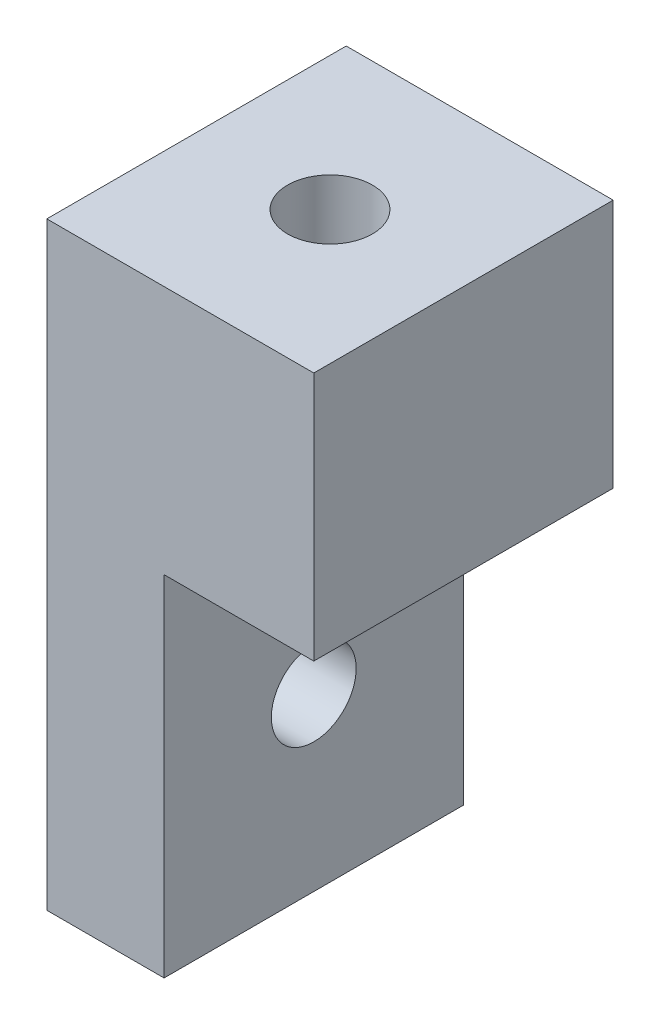
SolidWorks part; units mm, degrees
ref_plane "Front Plane" through (0, 0, 0) normal (0, 0, 1) x (1, 0, 0)
ref_plane "Top Plane" through (0, 0, 0) normal (0, 1, 0) x (1, 0, 0)
ref_plane "Right Plane" through (0, 0, 0) normal (1, 0, 0) x (0, 0, -1)
sketch "Sketch1" plane through (0, 0, 0) normal (0, 0, 1) x (1, 0, 0)
  line L0 (-0.325, -6) -> (-0.325, 1)
  line L1 (-2.675, 6) -> (2.675, 6)
  line L2 (-2.675, 6) -> (-2.675, -6)
  line L3 (-2.675, -6) -> (2.675, -6)
  line L4 (2.675, 6) -> (2.675, -6)
  line L5 (-2.675, 6) -> (2.675, -6) construction
  line L6 (-2.675, -6) -> (2.675, 6) construction
  line L7 (-0.325, 1) -> (2.675, 1)
  line L8 (2.675, 1) -> (2.675, -6)
  point P0 (0, 0)
  dimension "D1" = 0
  dimension "D2" = 12
  dimension "D3" = 3
  dimension "D4" = 2.35
  dimension "D5" = 5.35
  dimension "D6" = 5
extrude "Boss-Extrude1" add sketch "Sketch1" along normal blind 6 contours L7 L8 L3 L4 L1 L2 L0 region at (-0.5712, 1.2153, 0)
sketch "Sketch2" plane through (-2.675, 0, 0) normal (-1, 0, 0) x (0, 0, 1)
  line L0 (3, 0.8973) -> (3, -6) construction
  line L2 (6, -2.5513) -> (0, -2.5513) construction
  line L3 (0, 6) -> (0, -6) construction
  line L5 (6, -6) -> (0, -6)
  line L6 (6, -6) -> (6, 0.8973)
  line L7 (6, 0.8973) -> (0, 0.8973)
  line L8 (0, -6) -> (0, 0.8973)
  circle A0 centre (3, -2.5513) radius 0.85
  dimension "D1" = 1.7
  dimension "D2" = 3.4487
extrude "Cut-Extrude1" cut sketch "Sketch2" against normal through all contours A0
sketch "Sketch3" plane through (0, 6, 0) normal (0, 1, 0) x (1, 0, 0)
  line L0 (2.675, -6) -> (2.675, 0) construction
  line L1 (1.025, -6) -> (1.025, 0) construction
  line L2 (-2.675, -6) -> (2.675, -6) construction
  line L3 (-2.675, -3) -> (2.675, -3) construction
  line L4 (-2.675, -6) -> (-2.675, 0) construction
  line L5 (2.675, -6) -> (-0.625, -6) construction
  line L6 (-2.675, 0) -> (2.675, 0) construction
  line L7 (0, 0) -> (0, -6) construction
  circle A0 centre (0, -3) radius 0.85
  point P18 (0, -3)
  dimension "D1" = 1.7
  dimension "D2" = 3.3
extrude "Cut-Extrude2" cut sketch "Sketch3" against normal up to surface (5 mm away) up to face at (1.175, 1, 3)
